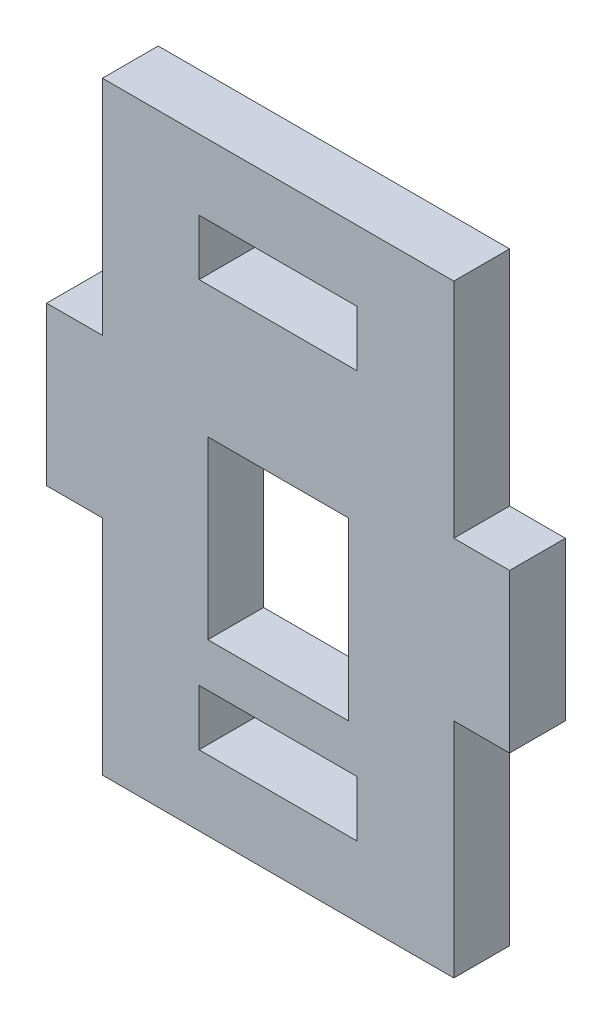
SolidWorks part; units mm, degrees
ref_plane "Front Plane" through (0, 0, 0) normal (0, 0, 1) x (1, 0, 0)
ref_plane "Top Plane" through (0, 0, 0) normal (0, 1, 0) x (1, 0, 0)
ref_plane "Right Plane" through (0, 0, 0) normal (1, 0, 0) x (0, 0, -1)
sketch "Sketch2" plane through (0, 0, 0) normal (0, 0, 1) x (1, 0, 0)
  line L0 (0, 0) -> (20, 0)
  line L1 (20, 0) -> (20, 12.675)
  line L2 (20, 12.675) -> (23.175, 12.675)
  line L3 (23.175, 12.675) -> (23.175, 21.675)
  line L4 (23.175, 21.675) -> (20, 21.675)
  line L5 (20, 21.675) -> (20, 34.35)
  line L6 (20, 34.35) -> (0, 34.35)
  line L7 (0, 34.35) -> (0, 21.675)
  line L8 (0, 21.675) -> (-3.175, 21.675)
  line L9 (-3.175, 21.675) -> (-3.175, 12.675)
  line L10 (-3.175, 12.675) -> (0, 12.675)
  line L11 (0, 12.675) -> (0, 0)
  line L12 (10, 50.5519) -> (10, -2.1862) construction
  line L13 (-3.175, 17.175) -> (57.251, 17.175) construction
  line L14 (10, 30.35) -> (5.5, 30.35)
  line L15 (5.5, 30.35) -> (5.5, 27.175)
  line L16 (5.5, 27.175) -> (14.5, 27.175)
  line L17 (10, 34.35) -> (10, 30.35) construction
  line L18 (14.5, 27.175) -> (14.5, 30.35)
  line L19 (14.5, 30.35) -> (10, 30.35)
  line L20 (14.5, 4) -> (10, 4)
  line L21 (14.5, 7.175) -> (14.5, 4)
  line L22 (5.5, 7.175) -> (14.5, 7.175)
  line L23 (5.5, 4) -> (5.5, 7.175)
  line L24 (10, 4) -> (5.5, 4)
  line L25 (10, 0) -> (10, 4) construction
  line L29 (14.5, 27.175) -> (20, 27.175)
  line L33 (10, 9.675) -> (14, 9.675)
  line L34 (14, 9.675) -> (14, 19.675)
  line L35 (14, 19.675) -> (6, 19.675)
  line L36 (6, 19.675) -> (6, 9.675)
  line L37 (6, 9.675) -> (10, 9.675)
  dimension "D1" = 3.175
  dimension "D2" = 9
  dimension "D3" = 20
  dimension "D4" = 20
  dimension "D5" = 4
  dimension "D6" = 8
  dimension "D7" = 10
  dimension "D8" = 2.5
extrude "Boss-Extrude1" add sketch "Sketch2" along normal mid plane 3.175 contours L19 L18 L5 L6 L7 L8 L9 L10 L11 L0 L1 L2 L3 L4 L16 L15 L14 L37 L36 L35 L34 L33 L20 L24 L23 L22 L21 region at (0.4329, 6.3375, 0)
